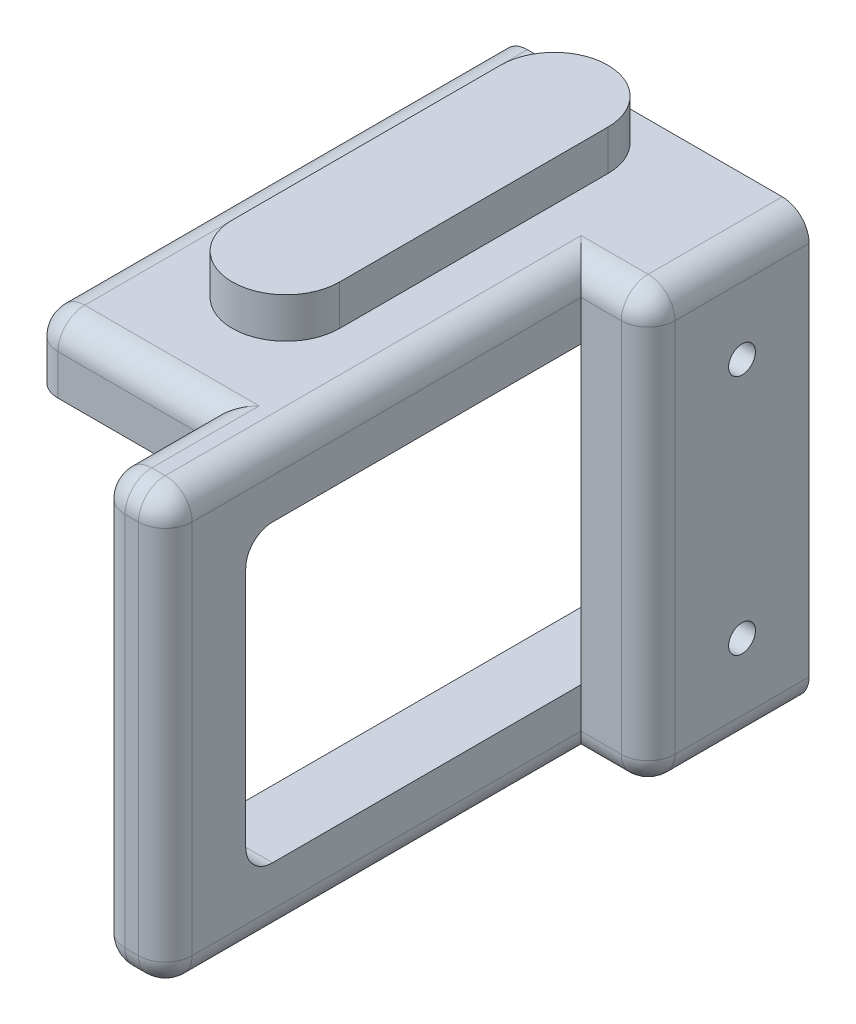
SolidWorks part; units mm, degrees
ref_plane "Front Plane" through (0, 0, 0) normal (0, 0, 1) x (1, 0, 0)
ref_plane "Top Plane" through (0, 0, 0) normal (0, 1, 0) x (1, 0, 0)
ref_plane "Right Plane" through (0, 0, 0) normal (1, 0, 0) x (0, 0, -1)
sketch "Sketch1" plane through (0, 0, 0) normal (1, 0, 0) x (0, 0, -1)
  line L0 (0, 22) -> (0, 27)
  line L1 (0, 0) -> (-35, 0)
  line L3 (0, 22) -> (-35, 22)
  line L4 (-37, 2) -> (-37, 20)
  line L5 (0, 27) -> (-41, 27)
  line L6 (-43, 25) -> (-43, -3)
  line L7 (-41, -5) -> (0, -5)
  line L8 (0, -5) -> (0, 0)
  arc A0 (-41, -5) -> (-43, -3) centre (-41, -3) cw
  arc A1 (-41, 27) -> (-43, 25) centre (-41, 25) ccw
  arc A2 (-37, 2) -> (-35, 0) centre (-35, 2) ccw
  arc A3 (-37, 20) -> (-35, 22) centre (-35, 20) cw
  point P15 (-37, 0)
  point P18 (-37, 22)
  dimension "D5" = 2
  dimension "D6" = 2
  dimension "D1" = 37
  dimension "D2" = 22
  dimension "D3" = 5
  dimension "D4" = 6
extrude "Boss-Extrude1" add sketch "Sketch1" against normal blind 5
sketch "Sketch2" plane through (0, 0, 0) normal (1, 0, 0) x (0, 0, -1)
  line L0 (0, 27) -> (-41, 27) construction
  line L1 (0, -5) -> (-12, -5)
  line L2 (0, -5) -> (0, 27)
  line L3 (0, 27) -> (-12, 27)
  line L4 (-12, -5) -> (-12, 27)
  dimension "D1" = 12
extrude "Boss-Extrude2" add sketch "Sketch2" along normal blind 5
sketch "Sketch3" plane through (5, 0, 0) normal (1, 0, 0) x (0, 0, -1)
  line L0 (-5, 22) -> (-5, 0) construction
  line L1 (-12, 22) -> (0, 22) construction
  line L2 (-12, 22) -> (-12, 0) construction
  line L3 (-12, 0) -> (0, 0) construction
  line L4 (0, 22) -> (0, 0) construction
  line L5 (-5, 11) -> (0, 11) construction
  circle A0 centre (-5, 2) radius 1
  circle A1 centre (-5, 20) radius 1
  dimension "D2" = 2
  dimension "D1" = 5
  dimension "D3" = 2
extrude "Cut-Extrude1" cut sketch "Sketch3" against normal up to next
fillet "Fillet1" radius 2 2 edges at (5, 27, 6) (5, -5, 6)
sketch "Sketch5" plane through (-5, 0, 0) normal (-1, 0, 0) x (0, 0, 1)
  line L0 (35, 22) -> (0, 22) construction
  line L5 (0, 27) -> (35, 27)
  line L6 (0, 27) -> (0, 22)
  line L7 (0, 22) -> (35, 22)
  line L8 (35, 27) -> (35, 22)
  arc A0 (37, 20) -> (35, 22) centre (35, 20) ccw construction
extrude "Boss-Extrude3" add sketch "Sketch5" along normal blind 13
fillet "Fillet2" radius 2 1 edges at (-18, 24.5, 35)
fillet "Fillet3" radius 2 15 edges at (-5, 27, 38) (-5, 26.4142, 42.4142) (-5, 11, 43) (-5, -5, 20.5) (0, 27, 26.5) (0, 26.4142, 42.4142) (0, 11, 43) (0, -5, 26.5) (1.5, 27, 12) (4.4142, 26.4142, 12) (1.5, -5, 12) (4.4142, -4.4142, 12) (-5, -4.4142, 42.4142) (0, -4.4142, 42.4142) (5, 11, 12)
fillet "Fillet4" radius 2 3 edges at (-18, 27, 16.5) (-17.4142, 27, 34.4142) (-9.5, 27, 35)
sketch "Encastre" plane through (0, 27, 0) normal (0, 1, 0) x (1, 0, 0)
  line L0 (-9, -5) -> (-9, -25) construction
  line L1 (-5, -5) -> (-5, -25)
  line L2 (-13, -5) -> (-13, -25)
  line L3 (-16, 0) -> (3, 0) construction
  line L4 (-2, -41) -> (-2, -10) construction
  arc A0 (-5, -5) -> (-13, -5) centre (-9, -5) ccw
  arc A1 (-13, -25) -> (-5, -25) centre (-9, -25) ccw
  point P2 (-9, -15)
  dimension "D5" = 4
  dimension "D1" = 20
  dimension "D2" = 8
  dimension "D3" = 5
  dimension "D4" = 3
extrude "Boss-Extrude4" add sketch "Encastre" along normal blind 3
